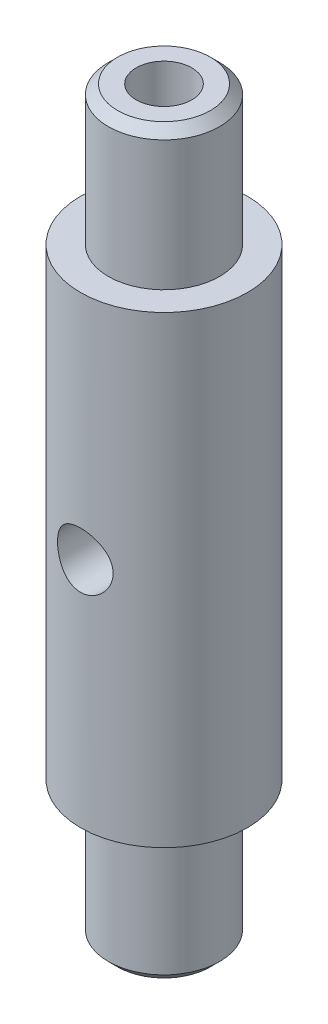
SolidWorks part; units mm, degrees
ref_plane "Front Plane" through (0, 0, 0) normal (0, 0, 1) x (1, 0, 0)
ref_plane "Top Plane" through (0, 0, 0) normal (0, 1, 0) x (1, 0, 0)
ref_plane "Right Plane" through (0, 0, 0) normal (1, 0, 0) x (0, 0, -1)
sketch "Sketch1" plane through (0, 0, 0) normal (0, 1, 0) x (1, 0, 0)
  circle A0 centre (0, 0) radius 6
  circle A1 centre (0, 0) radius 9
  dimension "D1" = 18
  dimension "D2" = 12
extrude "Boss-Extrude1" add sketch "Sketch1" along normal mid plane 50 contours A1
extrude "Boss-Extrude2" add sketch "Sketch1<3>" along normal mid plane 80 contours A0
sketch "Sketch1<3>" plane through (0, 0, 0) normal (0, 1, 0) x (1, 0, 0) same geometry as "Sketch1"
chamfer "Chamfer1" distance 1 angle 45 2 edges at (0, -40, 6) (0, 40, 6)
sketch "Sketch2" plane through (0, 0, 0) normal (0, 0, 1) x (1, 0, 0)
  circle A0 centre (0, 0) radius 3
  dimension "D1" = 6
extrude "Cut-Extrude1" cut sketch "Sketch2" against normal mid plane 80
sketch "Sketch3" plane through (0, 40, 0) normal (0, 1, 0) x (1, 0, 0)
  circle A0 centre (0, 0) radius 3
  dimension "D1" = 6
extrude "Cut-Extrude2" cut sketch "Sketch3" against normal blind 45
sketch "Sketch4" plane through (0, -5, 0) normal (0, 1, 0) x (1, 0, 0)
  circle A0 centre (0, 0) radius 3
  dimension "D1" = 6
extrude "Cut-Extrude3" cut sketch "Sketch4" against normal blind 2 draft 60
